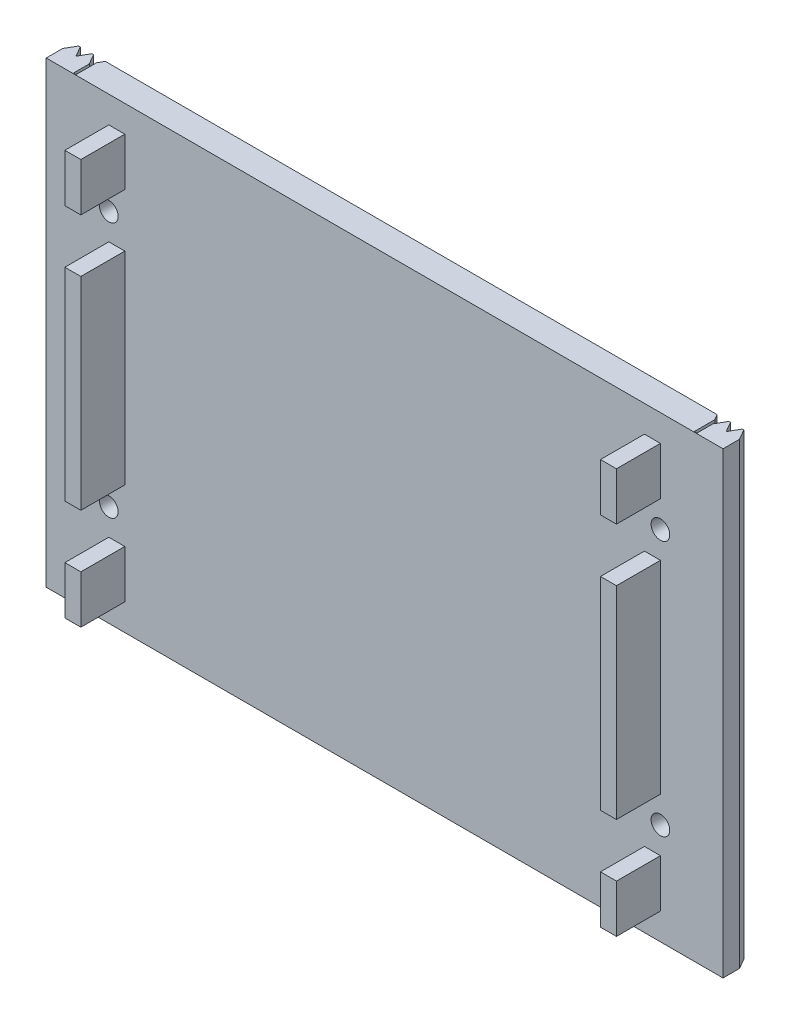
SolidWorks part; units mm, degrees
ref_plane "Front Plane" through (0, 0, 0) normal (0, 0, 1) x (1, 0, 0)
ref_plane "Top Plane" through (0, 0, 0) normal (0, 1, 0) x (1, 0, 0)
ref_plane "Right Plane" through (0, 0, 0) normal (1, 0, 0) x (0, 0, -1)
sketch "Sketch1" plane through (0, 0, 0) normal (0, 1, 0) x (1, 0, 0)
  line L0 (-127, 0) -> (-127, 10)
  line L1 (-127, 10) -> (-117, 10)
  line L2 (-117, 10) -> (-117, 0.2)
  line L4 (117, 0.2) -> (117, 10)
  line L5 (117, 10) -> (127, 10)
  line L6 (127, 10) -> (127, 0)
  line L7 (127, 0) -> (-127, 0)
  line L8 (-117, 0.2) -> (-116, 0.2)
  line L9 (-116, 0.2) -> (-116, 10)
  line L10 (-116, 10) -> (116, 10)
  line L11 (116, 10) -> (116, 0.2)
  line L12 (116, 0.2) -> (117, 0.2)
  dimension "D1" = 0.2
  dimension "D2" = 10
  dimension "D3" = 254
  dimension "D4" = 1
  dimension "D5" = 10
  dimension "D6" = 0
extrude "Main Body" add sketch "Sketch1" along normal blind 172
ref_plane "MidPlane" through (0, 0, -5) normal (0, 0, 1) x (1, 0, 0)
sketch "Sketch2" plane through (0, 0, -10) normal (0, 0, -1) x (-1, 0, 0)
  line L0 (-116, 172) -> (116, 172) construction
  line L1 (127, 172) -> (127, 0) construction
  circle A0 centre (103.5, 38) radius 3.5
  circle A1 centre (103.5, 134) radius 3.5
  dimension "D1" = 7
  dimension "D2" = 23.5
  dimension "D3" = 38
  dimension "D4" = 38
sketch "Sketch3" plane through (0, 0, -5) normal (0, 0, 1) x (1, 0, 0)
  circle A0 centre (-103.5, 134) radius 2.5
  circle A1 centre (-103.5, 38) radius 2.5
  dimension "D1" = 5
loft "Cut-Loft2" cut section "Sketch2" section "Sketch3" start constraint default connector at (-102.9873, 130.5378, -10) connector at (-103.2538, 131.5122, -5)
loft "Cut-Loft3" cut section "Sketch2<3>" section "Sketch3<3>" connector at (-100.0096, 38.2593, -10) connector at (-101.0031, 38.124, -5)
sketch "Sketch2<3>" plane through (0, 0, -10) normal (0, 0, -1) x (-1, 0, 0) same geometry as "Sketch2"
sketch "Sketch3<3>" plane through (0, 0, -5) normal (0, 0, 1) x (1, 0, 0) same geometry as "Sketch3"
mirror "Mirror1" about plane through (0, 0, -5) normal (0, 0, 1) of "Cut-Loft2", "Cut-Loft3"
mirror "Mirror2" about plane through (0, 0, 0) normal (1, 0, 0) of "Mirror1"
sketch "Sketch4" plane through (0, 0, 0) normal (0, 0, 1) x (1, 0, 0)
  line L0 (103.5, 38) -> (103.5, 48) construction
  line L1 (97.5, 124) -> (103.5, 124)
  line L2 (97.5, 124) -> (97.5, 48)
  line L3 (97.5, 48) -> (103.5, 48)
  line L4 (103.5, 124) -> (103.5, 48)
  line L5 (103.5, 124) -> (103.5, 134) construction
  line L6 (103.5, 134) -> (103.5, 144) construction
  line L7 (97.5, 144) -> (103.5, 144)
  line L8 (97.5, 144) -> (97.5, 162)
  line L9 (97.5, 162) -> (103.5, 162)
  line L10 (103.5, 144) -> (103.5, 162)
  line L11 (97.5, 28) -> (103.5, 28)
  line L12 (97.5, 28) -> (97.5, 10)
  line L13 (97.5, 10) -> (103.5, 10)
  line L14 (103.5, 28) -> (103.5, 10)
  line L15 (103.5, 38) -> (103.5, 28) construction
  line L16 (103.5, 162) -> (103.5, 172) construction
  line L17 (-127, 172) -> (127, 172) construction
  circle A1 centre (103.5, 134) radius 3.5 construction
  circle A2 centre (103.5, 38) radius 3.5 construction
  dimension "D1" = 6
  dimension "D2" = 20
extrude "Boss-Extrude1" add sketch "Sketch4" along normal blind 16.5
mirror "Mirror3" about plane through (0, 0, 0) normal (1, 0, 0) of "Boss-Extrude1"
sketch "Sketch5" plane through (0, 172, 0) normal (0, 1, 0) x (1, 0, 0)
  line L0 (129.5, 10.5) -> (127, 6.1699)
  line L1 (127, 6.1699) -> (124.5, 10.5)
  line L3 (124.5, 10.5) -> (129.5, 10.5)
  line L4 (127, 0) -> (127, 10) construction
  dimension "D1" = 5
  dimension "D2" = 0.5
extrude "Cut-Extrude1" cut sketch "Sketch5" against normal through all
pattern_linear "LPattern1" count 3 spacing 5 along (-1, 0, 0) of "Cut-Extrude1"
mirror "Mirror4" about plane through (0, 0, 0) normal (1, 0, 0) of "LPattern1"
